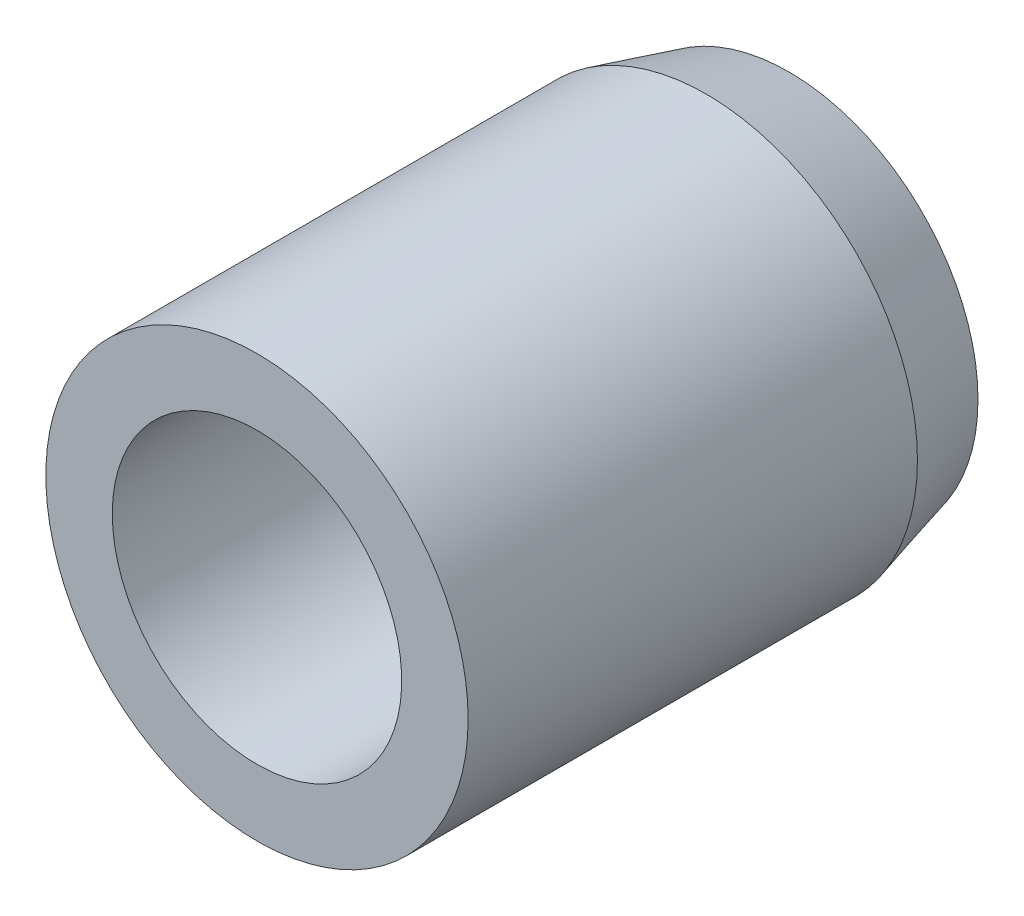
SolidWorks part; units mm, degrees
ref_plane "Plano frontal" through (0, 0, 0) normal (0, 0, 1) x (1, 0, 0)
ref_plane "Plano superior" through (0, 0, 0) normal (0, 1, 0) x (1, 0, 0)
ref_plane "Plano direito" through (0, 0, 0) normal (1, 0, 0) x (0, 0, -1)
sketch "Esboço1" plane through (0, 0, 0) normal (0, 0, 1) x (1, 0, 0)
  circle A0 centre (0, 0) radius 4.7625
  dimension "D1" = 9.525
extrude "Ressalto-extrusão1" add sketch "Esboço1" along normal blind 12
ref_axis "Eixo1" through (0, 0, 12) along (0, 0, -1)
chamfer "Chanfro1" distance 0.5 angle 75 1 edges at (4.7625, 0, 0) first distance on face at (4.7625, 0, 0)
hole_wizard "Broca de rosquear para tarraxa de 5/16-181" positions "Esboço4" profile "Esboço3" hole size "5/16-18" standard "Polegada Ansi" end condition through all
sketch "Esboço4" plane through (0, 0, 0) normal (0, 0, -1) x (-1, 0, 0)
  point P0 (0, 0)
sketch "Esboço3" plane through (0, 0, 0) normal (1, 0, 0) x (0, 1, 0)
  line L0 (0, 0) -> (0, 12)
  line L1 (0, 12) -> (3.2639, 12)
  line L2 (3.2639, 12) -> (3.2639, 0)
  line L5 (3.2639, 0) -> (0, 0)
  line L11 (0, -6.35) -> (0, 107.95) construction
  dimension "Thru Hole Dia." = 6.5278
  dimension "Thru Hole Depth" = 12
cosmetic thread "Representação de rosca1" parameters "D2"=7.9375
